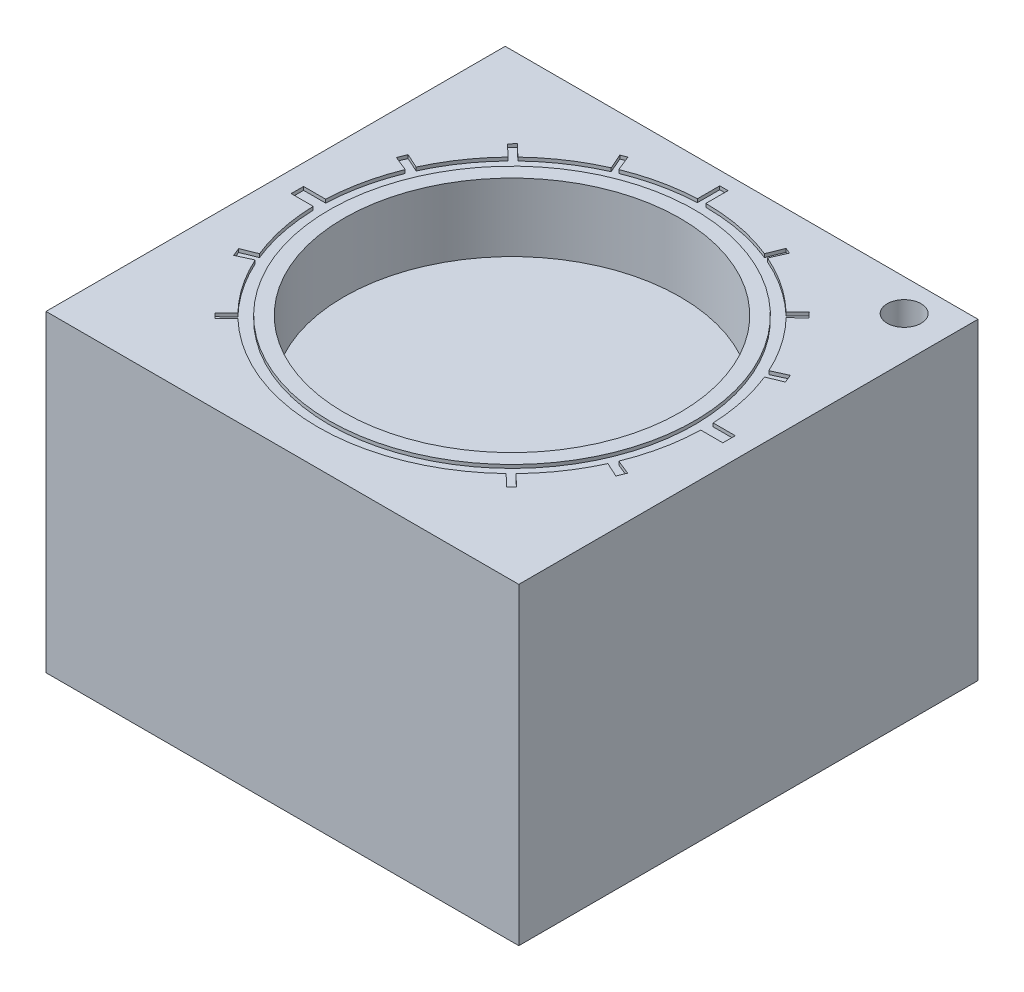
SolidWorks part; units mm, degrees
ref_plane "Front" through (0, 0, 0) normal (0, 0, 1) x (1, 0, 0)
ref_plane "Top" through (0, 0, 0) normal (0, 1, 0) x (1, 0, 0)
ref_plane "Right" through (0, 0, 0) normal (1, 0, 0) x (0, 0, -1)
sketch "Sketch1" plane through (0, 0, 0) normal (0, 1, 0) x (1, 0, 0)
  line L1 (0, 0) -> (-6.95, 0)
  line L2 (0, 0) -> (0, 6.75)
  line L3 (0, 6.75) -> (-6.95, 6.75)
  line L4 (-6.95, 0) -> (-6.95, 6.75)
  line L5 (0, 0) -> (-6.95, 6.75) construction
  line L6 (0, 6.75) -> (-6.95, 0) construction
  point P4 (-3.475, 3.375)
  dimension "D1" = 6.75
  dimension "D2" = 6.95
extrude "Boss-Extrude1" add sketch "Sketch1" along normal blind 4.6
sketch "Sketch3" plane through (0, 4.6, 0) normal (0, 1, 0) x (1, 0, 0)
  line L0 (-6.95, 6.75) -> (0, 0) construction
  line L1 (-2.4041, 6.0156) -> (-2.3127, 6.2411)
  line L3 (-3.5964, 6.2219) -> (-3.5964, 6.55)
  line L4 (-3.5964, 6.55) -> (-3.475, 6.55)
  line L6 (-0.6264, 3.3016) -> (-0.302, 3.3016)
  line L7 (-1.4304, 5.3598) -> (-1.2589, 5.5263)
  line L8 (-0.6276, 3.4839) -> (-0.302, 3.4839)
  line L11 (-0.302, 3.4839) -> (-0.302, 3.3016)
  line L12 (-1.2589, 5.5263) -> (-1.3306, 5.6001)
  line L13 (-0.7915, 3.3016) -> (-0.7903, 3.302) construction
  line L14 (-2.3127, 6.2411) -> (-2.2276, 6.2066)
  line L15 (-2.2276, 6.2066) -> (-2.3262, 5.9827)
  line L16 (-3.475, 6.2245) -> (-3.475, 6.55)
  line L18 (-1.3306, 5.6001) -> (-1.5035, 5.4324)
  line L19 (-0.8344, 4.4459) -> (-0.616, 4.5345)
  line L20 (-0.616, 4.5345) -> (-0.6657, 4.6571)
  line L21 (-0.6657, 4.6571) -> (-0.8827, 4.5581)
  line L22 (-6.95, 3.375) -> (0, 3.375) construction
  line L23 (-6.95, 6.75) -> (-6.95, 0) construction
  line L24 (0, 0) -> (0, 6.75) construction
  line L25 (-3.475, 6.75) -> (-3.475, 0) construction
  line L26 (0, 6.75) -> (-6.95, 6.75) construction
  line L27 (-6.95, 0) -> (0, 0) construction
  line L28 (-4.5459, 6.0156) -> (-4.6373, 6.2411)
  line L29 (-4.6373, 6.2411) -> (-4.7224, 6.2066)
  line L30 (-4.7224, 6.2066) -> (-4.6238, 5.9827)
  line L31 (-1.2589, 1.2237) -> (-1.3306, 1.1499)
  line L32 (-1.3306, 1.1499) -> (-1.5035, 1.3176)
  line L33 (-1.4304, 1.3902) -> (-1.2589, 1.2237)
  line L34 (-0.6657, 2.0929) -> (-0.8827, 2.1919)
  line L35 (-0.616, 2.2155) -> (-0.6657, 2.0929)
  line L36 (-0.8344, 2.3041) -> (-0.616, 2.2155)
  line L37 (-5.6194, 5.6001) -> (-5.4465, 5.4324)
  line L38 (-5.6911, 5.5263) -> (-5.6194, 5.6001)
  line L39 (-5.5196, 5.3598) -> (-5.6911, 5.5263)
  line L40 (-6.334, 4.5345) -> (-6.2843, 4.6571)
  line L41 (-6.2843, 4.6571) -> (-6.0673, 4.5581)
  line L42 (-6.1156, 4.4459) -> (-6.334, 4.5345)
  line L43 (-6.3224, 3.4839) -> (-6.648, 3.4839)
  line L44 (-6.648, 3.4839) -> (-6.648, 3.3016)
  line L45 (-6.3236, 3.3016) -> (-6.648, 3.3016)
  line L49 (-5.6911, 1.2237) -> (-5.6194, 1.1499)
  line L50 (-5.6194, 1.1499) -> (-5.4465, 1.3176)
  line L51 (-5.5196, 1.3902) -> (-5.6911, 1.2237)
  line L52 (-6.334, 2.2155) -> (-6.2843, 2.0929)
  line L53 (-6.2843, 2.0929) -> (-6.0673, 2.1919)
  line L54 (-6.1156, 2.3041) -> (-6.334, 2.2155)
  circle A0 centre (-3.475, 3.375) radius 2.4716
  circle A1 centre (-3.475, 3.375) radius 2.6857
  arc A2 (-3.5964, 6.2219) -> (-4.5459, 6.0156) centre (-3.475, 3.375) ccw
  arc A3 (-2.4041, 6.0156) -> (-3.475, 6.2245) centre (-3.475, 3.375) ccw
  arc A4 (-0.6276, 3.4839) -> (-0.8344, 4.4459) centre (-3.475, 3.375) ccw
  arc A5 (-0.8827, 4.5581) -> (-1.4304, 5.3598) centre (-3.475, 3.375) ccw
  arc A6 (-1.4304, 1.3902) -> (-0.8827, 2.1919) centre (-3.475, 3.375) ccw
  arc A7 (-0.8344, 2.3041) -> (-0.6264, 3.3016) centre (-3.475, 3.375) ccw
  arc A8 (-6.0673, 2.1919) -> (-5.5196, 1.3902) centre (-3.475, 3.375) ccw
  arc A9 (-5.4465, 1.3176) -> (-1.5035, 1.3176) centre (-3.475, 3.375) ccw
  arc A10 (-6.3236, 3.3016) -> (-6.1156, 2.3041) centre (-3.475, 3.375) ccw
  arc A11 (-6.1156, 4.4459) -> (-6.3224, 3.4839) centre (-3.475, 3.375) ccw
  arc A12 (-5.5196, 5.3598) -> (-6.0673, 4.5581) centre (-3.475, 3.375) ccw
  arc A13 (-4.6238, 5.9827) -> (-5.4465, 5.4324) centre (-3.475, 3.375) ccw
  circle A14 centre (-0.616, 6.2807) radius 0.2495
  arc A15 (-1.5035, 5.4324) -> (-2.3262, 5.9827) centre (-3.475, 3.375) ccw
  point P12 (-3.5357, 6.304)
  point P17 (-0.509, 3.3927)
extrude "Cut-Extrude3" cut sketch "Sketch3<3>" against normal blind 0.05 contours A15 L15 L14 L1 A3 L16 L4 L3 A2 L28 L29 L30 A13 L37 L38 L39 A12 L41 L40 L42 A11 L43 L44 L45 A10 L54 L52 L53 A8 L51 L49 L50 A9 L32 L31 L33 A6 L34 L35 L36 A7 L6 L11 L8 A4 L19 L20 L21 A5 L7 L12 L18 | A1
sketch "Sketch3<3>" plane through (0, 4.6, 0) normal (0, 1, 0) x (1, 0, 0) same geometry as "Sketch3"
extrude "Cut-Extrude4" cut sketch "Sketch3<4>" against normal blind 1 contours A0 region at (-3.475, 4.6, -3.375)
sketch "Sketch3<4>" plane through (0, 4.6, 0) normal (0, 1, 0) x (1, 0, 0) same geometry as "Sketch3"
extrude "Cut-Extrude5" cut sketch "Sketch3" against normal blind 0.5 contours A14 region at (-0.616, 4.6, -6.2807)
